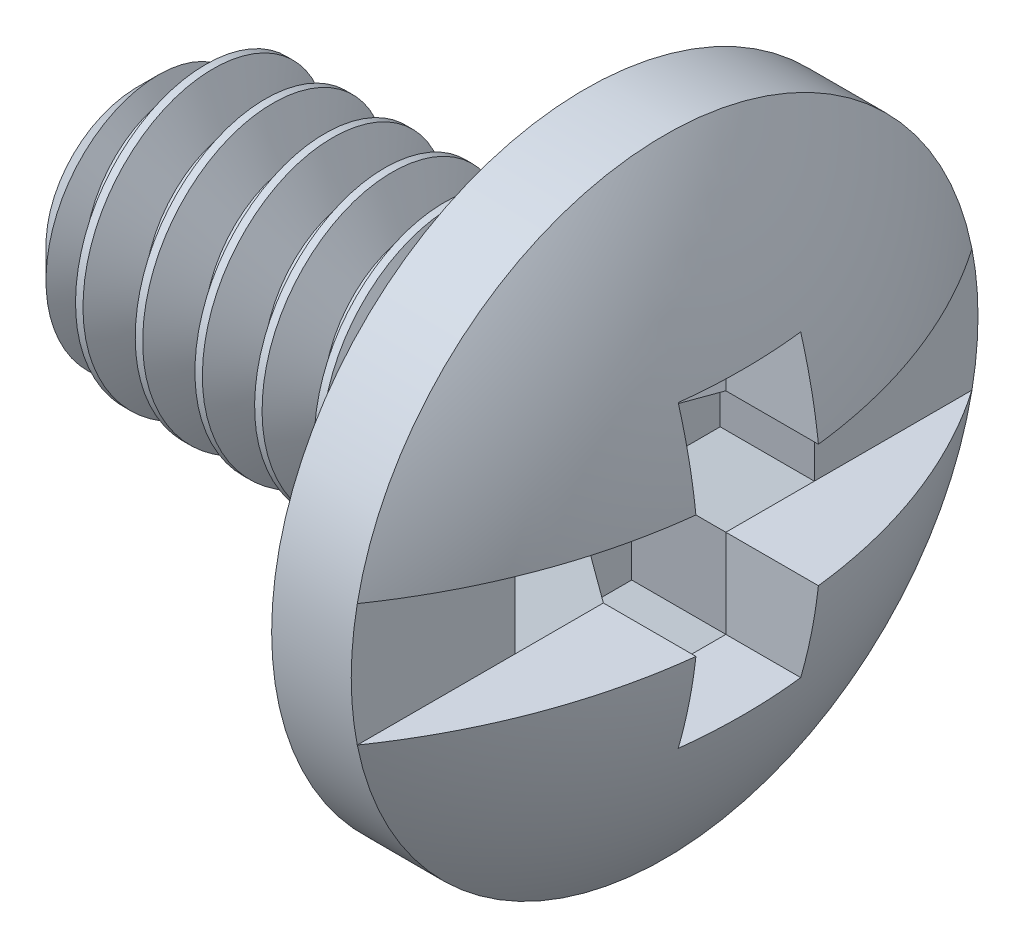
SolidWorks part; units mm, degrees
ref_plane "Front Plane" through (0, 0, 0) normal (0, 0, 1) x (1, 0, 0)
ref_plane "Top Plane" through (0, 0, 0) normal (0, 1, 0) x (1, 0, 0)
ref_plane "Right Plane" through (0, 0, 0) normal (1, 0, 0) x (0, 0, -1)
sketch "Sketch1" plane through (0, 0, 0) normal (0, 0, 1) x (1, 0, 0)
  line L0 (0, 0) -> (7.9375, 0) construction
  line L1 (0, 2.413) -> (0, -2.413) construction
  line L2 (7.9375, 5.5562) -> (7.9375, -5.5562) construction
  line L3 (7.9375, 0) -> (11.1125, 0) construction
  line L4 (-6.35, 3.175) -> (-6.35, -3.175) construction
  line L5 (-6.35, 0) -> (-44.45, 0) construction
  line L6 (-44.45, 5.5563) -> (-44.45, -5.5563) construction
  line L7 (-6.35, 2.413) -> (-15.875, 2.413) construction
  line L8 (-15.875, 2.413) -> (-15.875, -2.413) construction
  line L9 (-15.875, -2.413) -> (-6.35, -2.413) construction
  line L10 (-44.45, 0) -> (-47.625, 0) construction
  line L11 (7.9375, -5.5562) -> (-44.45, -5.5563) construction
  point P18 (-15.875, 0)
  point P19 (-18.2563, -5.5563)
  point P21 (2.6458, -2.413)
  dimension "Screw Dia" = 4.826
  dimension "Screw Length" = 7.9375
  dimension "Head Dia" = 11.1125
  dimension "Head Height" = 3.175
  dimension "D1" = 6.35
  dimension "Barrel Dia" = 6.35
  dimension "Thread Depth" = 9.525
  dimension "Barrel Length" = 38.1
  dimension "D2" = 2.6458
ref_plane "Plane1" through (11.1125, 0, 0) normal (1, 0, 0) x (0, 0, -1)
sketch "Sketch2" plane through (0, 0, 0) normal (1, 0, 0) x (0, 0, -1)
  circle A0 centre (0, 0) radius 2.413
extrude "Boss-Extrude1" add sketch "Sketch2" along normal up to vertex (7.9375 mm away) up to point (7.9375, 0, 0)
sketch "Sketch4" plane through (0, 0, 0) normal (-1, 0, 0) x (0, 0, 1)
  circle A1 centre (0, 0) radius 2.413
  circle A2 centre (0, 0) radius 2.413
  dimension "D1" = 0
curve "Helix/Spiral1" pitch 1.0583 height 8.9958 turns 8.5 parameters "Pitch"=1.0583
chamfer "Chamfer1" distance 0.7937 angle 45 1 edges at (0, 0, -2.413)
sketch "Sketch5" plane through (0, 0, 0) normal (0, 0, 1) x (1, 0, 0)
  line L0 (0, 2.413) -> (-0.926, 2.413)
  line L1 (0, 2.413) -> (-0.3969, 1.7256)
  line L2 (-0.3969, 1.7256) -> (-0.5292, 1.7256)
  line L3 (-0.5292, 1.7256) -> (-0.926, 2.413)
  line L4 (-0.463, 1.7256) -> (-0.463, 2.413) construction
  line L5 (-0.1984, 2.0693) -> (-0.7276, 2.0693) construction
  dimension "D1" = 0.1323
  dimension "D2" = 0.5292
  dimension "D3" = 60
sweep "Cut-Sweep1" cut profiles "Sketch5" path "Helix/Spiral1"
sketch "Sketch6" plane through (0, 0, 0) normal (0, 0, 1) x (1, 0, 0)
  line L0 (7.9375, 0) -> (7.9375, 5.5562)
  line L1 (7.9375, 5.5562) -> (9.3486, 5.5562)
  line L2 (11.1125, 0) -> (11.1125, 5.5562) construction
  line L3 (11.1125, 0) -> (7.9375, 0) construction
  line L5 (7.9375, 0) -> (11.1125, 0)
  line L6 (11.1125, 0) -> (11.1125, -1.9812) construction
  arc A0 (11.1125, 0) -> (9.3486, 5.5562) centre (1.4795, 0) ccw
  point P6 (8.2903, 5.5562)
  point P10 (11.1125, -1.9812)
  dimension "D1" = 1.4111
  dimension "D2" = 1.0583
revolve "Revolve1" add sketch "Sketch6" angle 360 about L3
sketch "Sketch17" plane through (11.1125, 0, 0) normal (1, 0, 0) x (0, 0, -1)
  line L0 (-5.5562, 0) -> (5.5562, 0) construction
  line L1 (-5.5562, 1.0858) -> (5.5562, 1.0858)
  line L2 (-5.5562, 1.0858) -> (-5.5562, -1.0858)
  line L3 (-5.5562, -1.0858) -> (5.5562, -1.0858)
  line L4 (5.5562, 1.0858) -> (5.5562, -1.0858)
  circle A0 centre (0, 0) radius 5.5562 construction
  dimension "D1" = 2.1717
extrude "Cut-Extrude5" cut sketch "Sketch17" against normal up to vertex (1.7639 mm away) up to point (9.3486, 5.5562, 0)
sketch "Sketch18" plane through (9.3486, 0, 0) normal (1, 0, 0) x (0, 0, -1)
  line L0 (0, 0) -> (0, 2.6543) construction
  line L1 (-1.0858, 2.6543) -> (1.0859, 2.6543)
  line L2 (-1.0858, 2.6543) -> (-1.0858, -2.6543)
  line L3 (-1.0858, -2.6543) -> (1.0858, -2.6543)
  line L4 (1.0859, 2.6543) -> (1.0858, -2.6543)
  line L5 (0, 0) -> (1.0859, 0) construction
  dimension "D1" = 2.1717
  dimension "D2" = 5.3086
extrude "Cut-Extrude6" cut sketch "Sketch18" along normal through all and the other way up to vertex (1.0583 mm away) draft 30
sketch "Sketch19" plane through (9.3486, 0, 0) normal (1, 0, 0) x (0, 0, -1)
  line L0 (-2.6543, 0) -> (2.6543, 0) construction
  line L1 (-2.6543, 1.0859) -> (2.6543, 1.0859)
  line L2 (-2.6543, 1.0859) -> (-2.6543, -1.0858)
  line L3 (-2.6543, -1.0858) -> (2.6543, -1.0859)
  line L4 (2.6543, 1.0859) -> (2.6543, -1.0859)
  line L5 (-1.0858, 2.6543) -> (1.0859, 2.6543) construction
  line L6 (-1.0858, 2.6543) -> (-1.0858, -2.6543) construction
extrude "Cut-Extrude7" cut sketch "Sketch19" against normal up to vertex (1.0583 mm away) draft 30 up to point (8.2903, 5.5562, 0)
equation "\"D1@Sketch5\" = \"Pitch@Helix/Spiral1\"*.125"
equation "\"D2@Sketch5\" = \"Pitch@Helix/Spiral1\"*.50"
equation "\"D3@Helix/Spiral1\" = \"Screw Length@Sketch1\"+\"Pitch@Helix/Spiral1\""
equation "\"D1@Chamfer1\" = \"Pitch@Helix/Spiral1\"*.750"
equation "\"D1@Sketch6\" = \"Head Height@Sketch1\"/2.250"
equation "\"D2@Sketch1\" = \"Pitch@Helix/Spiral1\"*2.50"
equation "\"D1@Sketch17\" = \"Screw Dia@Sketch1\"*.45"
equation "\"D1@Sketch18\" = \"D1@Sketch17\"*1"
equation "\"D2@Sketch18\" = \"Screw Dia@Sketch1\"*1.1"
equation "\"D2@Sketch6\" = \"D1@Sketch6\"*.750"
